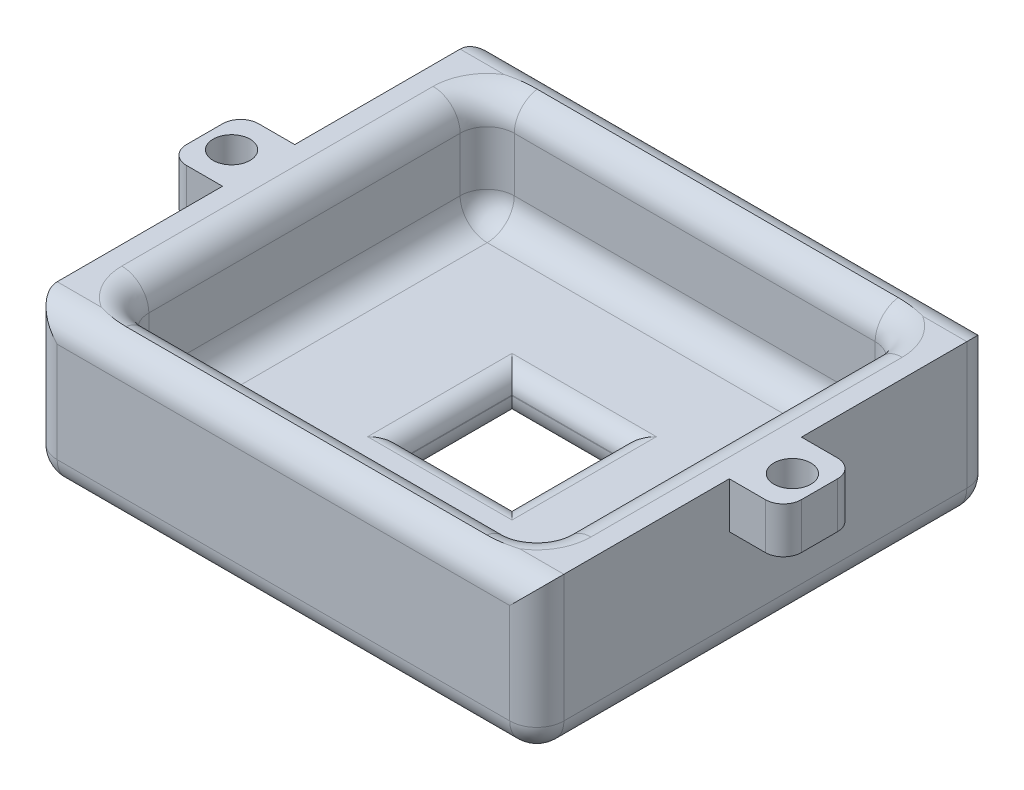
SolidWorks part; units mm, degrees
ref_plane "Front Plane" through (0, 0, 0) normal (0, 0, 1) x (1, 0, 0)
ref_plane "Top Plane" through (0, 0, 0) normal (0, 1, 0) x (1, 0, 0)
ref_plane "Right Plane" through (0, 0, 0) normal (1, 0, 0) x (0, 0, -1)
sketch "Sketch1" plane through (0, 0, 0) normal (0, 1, 0) x (1, 0, 0)
  line L1 (-18.545, 19.5488) -> (27.455, 19.5488)
  line L2 (-18.545, 19.5488) -> (-18.545, -20.9512)
  line L3 (-18.545, -20.9512) -> (27.455, -20.9512)
  line L4 (27.455, 19.5488) -> (27.455, -20.9512)
  line L5 (-23.625, 24.6288) -> (32.535, 24.6288)
  line L6 (-23.625, 24.6288) -> (-23.625, -26.0312)
  line L7 (-23.625, -26.0312) -> (32.535, -26.0312)
  line L8 (32.535, 24.6288) -> (32.535, -26.0312)
  dimension "D1" = 46
  dimension "D2" = 40.5
  dimension "D3" = 5.08
  dimension "D4" = 5.08
  dimension "D5" = 5.08
  dimension "D6" = 5.08
extrude "Boss-Extrude1" add sketch "Sketch1" along normal blind 12
sketch "Sketch2" plane through (0, 0, 0) normal (0, -1, 0) x (1, 0, 0)
  line L1 (32.535, 26.0312) -> (-23.625, 26.0312)
  line L2 (32.535, 26.0312) -> (32.535, -24.6288)
  line L3 (32.535, -24.6288) -> (-23.625, -24.6288)
  line L4 (-23.625, 26.0312) -> (-23.625, -24.6288)
extrude "Boss-Extrude2" add sketch "Sketch2" along normal blind 5.08
sketch "Sketch3" plane through (0, -5.08, 0) normal (0, -1, 0) x (1, 0, 0)
  line L0 (4.455, -24.6288) -> (4.455, 26.0312) construction
  line L1 (10.455, -5.2988) -> (-1.545, -5.2988)
  line L2 (10.455, -5.2988) -> (10.455, 6.7012)
  line L3 (10.455, 6.7012) -> (-1.545, 6.7012)
  line L4 (-1.545, -5.2988) -> (-1.545, 6.7012)
  line L5 (-23.625, -24.6288) -> (32.535, -24.6288) construction
  line L6 (32.535, 26.0312) -> (-23.625, 26.0312) construction
  line L7 (32.535, 0.7012) -> (-23.625, 0.7013) construction
  line L8 (32.535, -24.6288) -> (32.535, 26.0312) construction
  line L9 (-23.625, 26.0312) -> (-23.625, -24.6288) construction
  dimension "D1" = 12
  dimension "D2" = 12
  dimension "D3" = 6
  dimension "D4" = 6
extrude "Cut-Extrude1" cut sketch "Sketch3" against normal blind 5.08
sketch "Sketch4" plane through (32.535, 0, 0) normal (1, 0, 0) x (0, 0, -1)
  line L0 (-26.0313, 12) -> (24.6287, 12) construction
  line L1 (-4.7013, 12) -> (3.2987, 12)
  line L2 (-4.7013, 12) -> (-4.7013, 6.92)
  line L3 (-4.7013, 6.92) -> (3.2987, 6.92)
  line L4 (3.2987, 12) -> (3.2987, 6.92)
  line L5 (-0.7013, -5.08) -> (-0.7013, 12) construction
  line L6 (24.6287, -5.08) -> (-26.0313, -5.08) construction
  dimension "D1" = 8
  dimension "D2" = 4
  dimension "D3" = 5.08
extrude "Boss-Extrude3" add sketch "Sketch4" along normal blind 6
sketch "Sketch5" plane through (-23.625, 0, 0) normal (-1, 0, 0) x (0, 0, 1)
  line L0 (-24.6288, 12) -> (26.0312, 12) construction
  line L1 (4.7012, 12) -> (-3.2988, 12)
  line L2 (4.7012, 12) -> (4.7012, 6.92)
  line L3 (4.7012, 6.92) -> (-3.2988, 6.92)
  line L4 (-3.2988, 12) -> (-3.2988, 6.92)
  line L5 (0.7013, -5.08) -> (0.7013, 12) construction
  line L7 (26.0312, -5.08) -> (-24.6288, -5.08) construction
  dimension "D1" = 8
  dimension "D2" = 4
  dimension "D3" = 5.08
extrude "Boss-Extrude4" add sketch "Sketch5" along normal blind 6
sketch "Sketch6" plane through (0, 6.92, 0) normal (0, -1, 0) x (1, 0, 0)
  line L0 (38.535, 4.7012) -> (32.535, 4.7012) construction
  line L1 (38.535, 4.7012) -> (38.535, -3.2988) construction
  line L2 (-29.625, 4.7012) -> (-23.625, 4.7012) construction
  line L3 (-29.625, -3.2988) -> (-29.625, 4.7012) construction
  circle A0 centre (35.535, 0.7012) radius 2.05
  circle A1 centre (-26.625, 0.7012) radius 2.05
  dimension "D3" = 4.1
  dimension "D6" = 4.1
  dimension "D1" = 4
  dimension "D2" = 3
  dimension "D4" = 4
  dimension "D5" = 3
extrude "Cut-Extrude2" cut sketch "Sketch6" against normal blind 6
fillet "Fillet1" radius 3 26 edges at (4.455, 12, 26.0312) (32.535, 3.46, 26.0312) (-23.625, 3.46, 26.0312) (4.455, 12, 20.9512) (4.455, 0, 20.9512) (4.455, 12, -19.5488) (4.455, 0, -19.5488) (-18.545, 6, 20.9512) (-18.545, 12, 0.7012) (-18.545, 6, -19.5488) (-18.545, 0, 0.7012) (27.455, 6, -19.5488) (27.455, 12, 0.7012) (27.455, 6, 20.9512) (27.455, 0, 0.7012) (4.455, 12, -24.6288) (-23.625, 3.46, -24.6288) (32.535, 3.46, -24.6288) (4.455, -5.08, -24.6288) (-23.625, -5.08, 0.7012) (4.455, -5.08, 26.0312) (32.535, -5.08, 0.7012) (-1.545, -5.08, 0.7012) (4.455, -5.08, -5.2988) (10.455, -5.08, 0.7012) (4.455, -5.08, 6.7012)
fillet "Fillet2" radius 2 4 edges at (-29.625, 9.46, -3.2988) (-29.625, 9.46, 4.7012) (38.535, 9.46, -3.2988) (38.535, 9.46, 4.7012)
fillet "Fillet3" radius 2 4 edges at (-1.545, 0, 0.7012) (4.455, 0, 6.7012) (10.455, 0, 0.7012) (4.455, 0, -5.2988)
